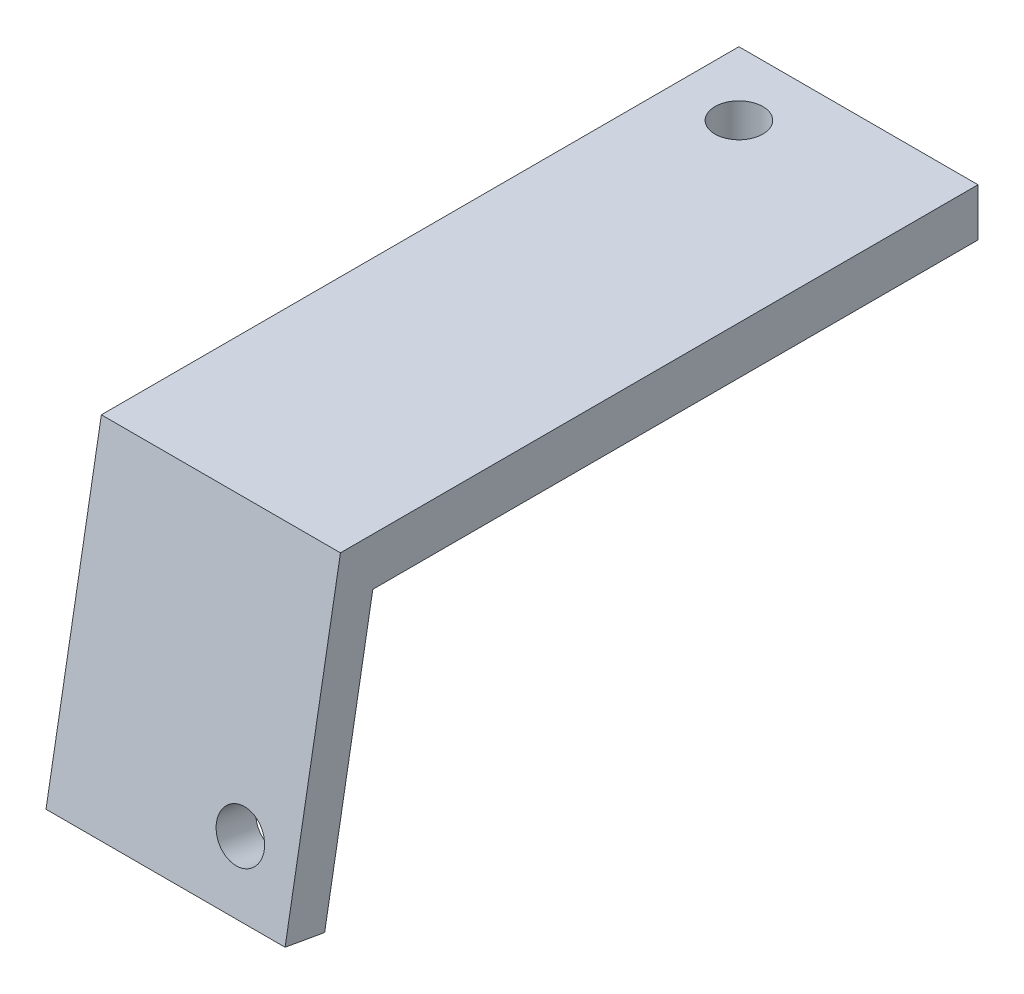
SolidWorks part; units mm, degrees
ref_plane "Front Plane" through (0, 0, 0) normal (0, 0, 1) x (1, 0, 0)
ref_plane "Top Plane" through (0, 0, 0) normal (0, 1, 0) x (1, 0, 0)
ref_plane "Right Plane" through (0, 0, 0) normal (1, 0, 0) x (0, 0, -1)
sketch "Sketch1" plane through (0, 0, 0) normal (0, 1, 0) x (1, 0, 0)
  line L1 (-7.5, -20) -> (7.5, -20)
  line L2 (-7.5, -20) -> (-7.5, 20)
  line L3 (-7.5, 20) -> (7.5, 20)
  line L4 (7.5, -20) -> (7.5, 20)
  line L5 (-7.5, -20) -> (7.5, 20) construction
  line L6 (-7.5, 20) -> (7.5, -20) construction
  circle A0 centre (-3.5, 16) radius 1.5
  point P0 (0, 0)
  dimension "D3" = 3
  dimension "D1" = 15
  dimension "D2" = 40
  dimension "D4" = 4
  dimension "D5" = 4
extrude "Boss-Extrude1" add sketch "Sketch1" along normal blind 3
ref_plane "Plane1" through (0, -0.5107, 0.09) normal (0, 0.9848, -0.1736) x (1, 0, 0)
sketch "Sketch2" plane through (0, -0.5107, 0.09) normal (0, 0.9848, -0.1736) x (1, 0, 0)
  line L0 (-7.5, -20.2171) -> (-7.5, -19.6962) construction
  line L1 (-7.5, -17.6962) -> (7.5, -17.6962)
  line L2 (-7.5, -17.6962) -> (-7.5, -20.2171)
  line L3 (-7.5, -20.2171) -> (7.5, -20.2171)
  line L4 (7.5, -17.6962) -> (7.5, -20.2171)
  line L7 (-7.5, -19.6962) -> (7.5, -19.6962) construction
  dimension "D1" = 2
extrude "Boss-Extrude2" add sketch "Sketch2" against normal blind 20
sketch "Sketch3" plane through (0, 3.5107, 19.91) normal (0, 0.1736, 0.9848) x (1, 0, 0)
  line L1 (-7.5, -20.5185) -> (7.5, -20.5185) construction
  circle A0 centre (4, -16.5185) radius 1.5
  ellipse E0 centre (-3.5, 5.7328) end of major axis (-5, 5.7328) minor radius 0.2605 construction
  dimension "D1" = 3
  dimension "D2" = 4
  dimension "D3" = 7.5
extrude "Cut-Extrude1" cut sketch "Sketch3" against normal blind 10
